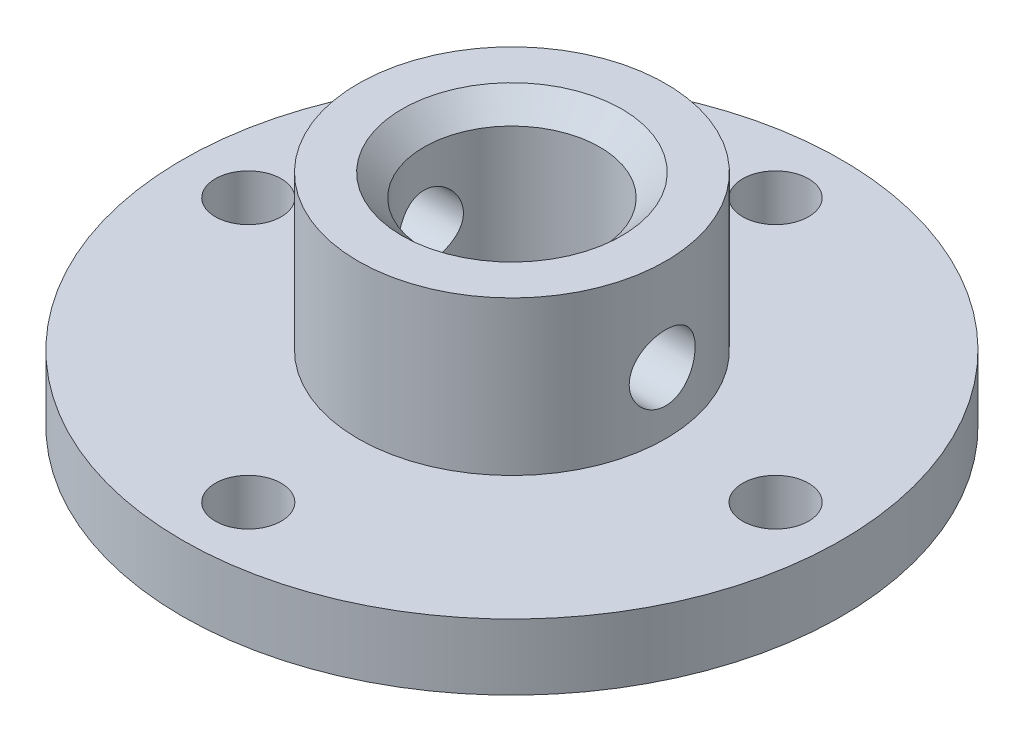
SolidWorks part; units mm, degrees
ref_plane "前视基准面" through (0, 0, 0) normal (0, 0, 1) x (1, 0, 0)
ref_plane "上视基准面" through (0, 0, 0) normal (0, 1, 0) x (1, 0, 0)
ref_plane "右视基准面" through (0, 0, 0) normal (1, 0, 0) x (0, 0, -1)
sketch "草图1" plane through (0, 0, 0) normal (0, 1, 0) x (1, 0, 0)
  circle A0 centre (0, 0) radius 15
  circle A1 centre (0, 0) radius 4
  dimension "D1" = 30
  dimension "D2" = 8
extrude "凸台-拉伸1" add sketch "草图1" along normal blind 3 contours A1 | A0 region at (0, 0, 0)
sketch "草图2" plane through (0, 3, 0) normal (0, 1, 0) x (1, 0, 0)
  circle A0 centre (0, 0) radius 4
  circle A1 centre (0, 0) radius 7
  dimension "D1" = 14
  dimension "D2" = 8
extrude "凸台-拉伸2" add sketch "草图2" along normal blind 7
ref_axis "基准轴1" through (0, 9, 0) along (0, -1, 0)
sketch "草图4" plane through (0, 0, 0) normal (0, -1, 0) x (-1, 0, 0)
  line L0 (0, 0) -> (0, -10.4165)
ref_plane "基准面1" through (0, 0, 0) normal (-1, 0, 0) x (0, 0, 1)
sketch "草图5" plane through (0, 0, 0) normal (-1, 0, 0) x (0, 0, 1)
  line L0 (7, 3) -> (-7, 3) construction
  line L1 (-7, 10) -> (-7, 3) construction
  circle A0 centre (0, 5.8) radius 1.5
  dimension "D1" = 3
  dimension "D2" = 2.8
  dimension "D3" = 7
extrude "切除-拉伸1" cut sketch "草图5" along normal blind 13 and the other way blind 12
sketch "草图6" plane through (0, 0, 0) normal (0, -1, 0) x (1, 0, 0)
  circle A0 centre (0, 0) radius 4
  dimension "D1" = 8
sketch "草图7" plane through (0, 3, 0) normal (0, 1, 0) x (1, 0, 0)
  circle A0 centre (0, -12) radius 1.5
  circle A1 centre (-12, 0) radius 1.5
  circle A2 centre (0, 12) radius 1.5
  circle A3 centre (12, 0) radius 1.5
  point P12 (0, 0)
  dimension "D1" = 0
  dimension "D2" = 12
  dimension "D3" = 3
  dimension "D4" = 4
extrude "切除-拉伸3" cut sketch "草图7" against normal blind 4 contours A3 | A0 | A1 | A2 region at (12, 3, 0)
chamfer "倒角1" distance 1 angle 45 1 edges at (0, 10, 4)
